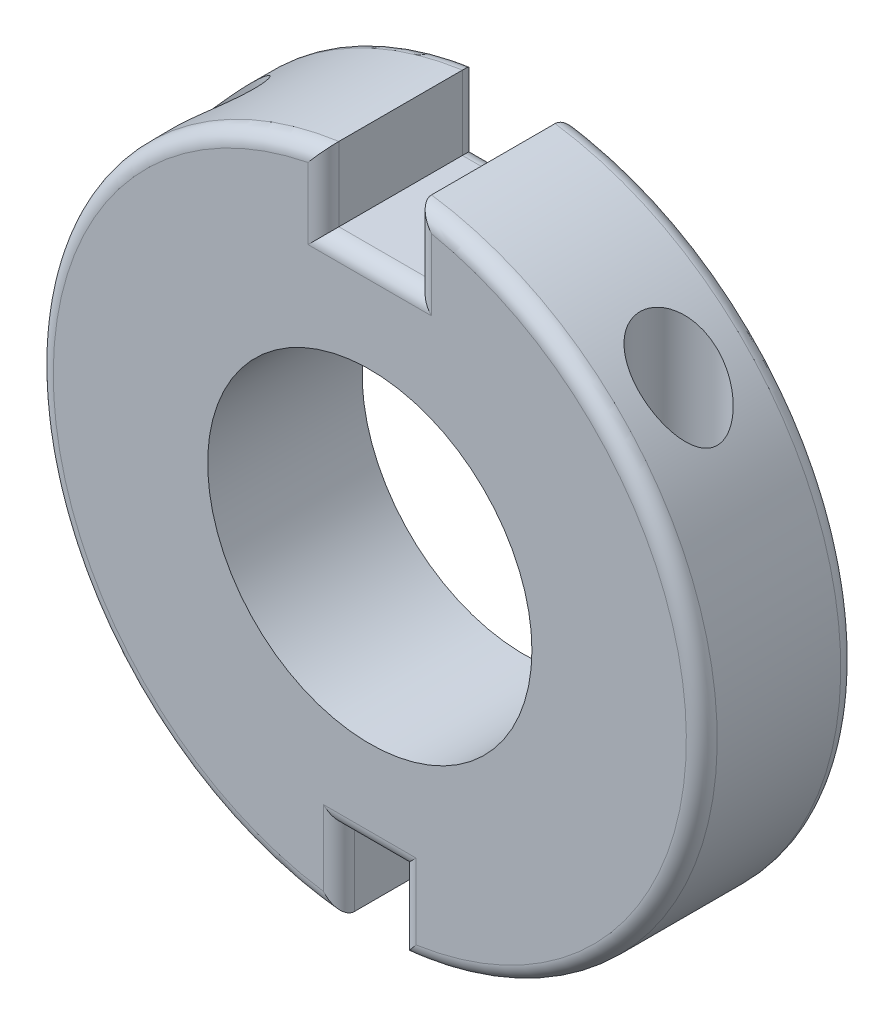
SolidWorks part; units mm, degrees
ref_plane "Plan de face" through (0, 0, 0) normal (0, 0, 1) x (1, 0, 0)
ref_plane "Plan de dessus" through (0, 0, 0) normal (0, 1, 0) x (1, 0, 0)
ref_plane "Plan de droite" through (0, 0, 0) normal (1, 0, 0) x (0, 0, -1)
sketch "Esquisse1" plane through (0, 0, 0) normal (0, 0, 1) x (1, 0, 0)
  line L0 (0, -21.5) -> (0, 21.5) construction
  line L1 (3, 16.5) -> (-3, 16.5)
  line L2 (-3, 16.5) -> (-3, 21.2897)
  line L3 (2, -16.4068) -> (-2, -16.4068)
  line L4 (-2, -16.4068) -> (-2, -21.4068)
  line L5 (-21.5, 0) -> (21.5, 0)
  line L6 (3, 16.5) -> (3, 21.2897)
  line L7 (2, -16.4068) -> (2, -21.4068)
  circle A0 centre (0, 0) radius 21.5
  circle A1 centre (0, 0) radius 10.5
  point P16 (0, 16.5)
  point P17 (0, -16.4068)
  dimension "D1" = 43
  dimension "D2" = 21
  dimension "D3" = 3
  dimension "D4" = 5
  dimension "D5" = 2
  dimension "D6" = 5
extrude "Boss.-Extru.1" add sketch "Esquisse1" along normal blind 10 contours A1 L0 L1 L2 A0 L5 | L0 A1 L5 A0 L6 L1 | L0 L3 L7 A0 L5 A1 | L3 L0 A1 L5 A0 L4 region at (-10.9517, -10.2697, 0) region at (10.9517, -10.2697, 0) region at (-11.1013, 10.1136, 0) region at (11.1013, 10.1136, 0)
sketch "Esquisse2" plane through (0, 0, 0) normal (0, 1, 0) x (1, 0, 0)
  line L0 (0, -10) -> (0, 0) construction
  line L1 (2, -10) -> (-2, -10) construction
  line L2 (-21.5, -5) -> (21.5, -5) construction
  line L3 (-21.5, 0) -> (-21.5, -10) construction
  line L4 (21.5, -10) -> (21.5, 0) construction
  circle A0 centre (15, -5) radius 1.25
  circle A1 centre (15, -5) radius 2.5
  circle A2 centre (-15, -5) radius 2.5
  circle A3 centre (-15, -5) radius 1.25
  point P17 (0, 0)
  dimension "D2" = 2.5
  dimension "D3" = 5
  dimension "D1" = 15
extrude "Enlèv. mat.-Extru.1" cut sketch "Esquisse2" against normal blind 12.5 and the other way blind 20 contours A0 | A3 region at (15, 0, 5) region at (-15, 0, 5)
extrude "Enlèv. mat.-Extru.2" cut sketch "Esquisse2<5>" along normal blind 10 from offset 7.5 contours A1 A0 | A2 | A3 region at (12.5707, 0, 5)
sketch "Esquisse2<5>" plane through (0, 0, 0) normal (0, 1, 0) x (1, 0, 0) same geometry as "Esquisse2"
fillet "Congé1" radius 1 16 edges at (-2, -18.9068, 0) (0, -16.4068, 0) (2, -18.9068, 0) (-21.4941, -0.5034, 0) (-3, 18.8948, 0) (0, 16.5, 0) (3, 18.8948, 0) (21.4941, -0.5034, 0) (-2, -18.9068, 10) (0, -16.4068, 10) (2, -18.9068, 10) (-3, 18.8948, 10) (0, 16.5, 10) (3, 18.8948, 10) (21.4941, -0.5034, 10) (-21.4941, -0.5034, 10)
